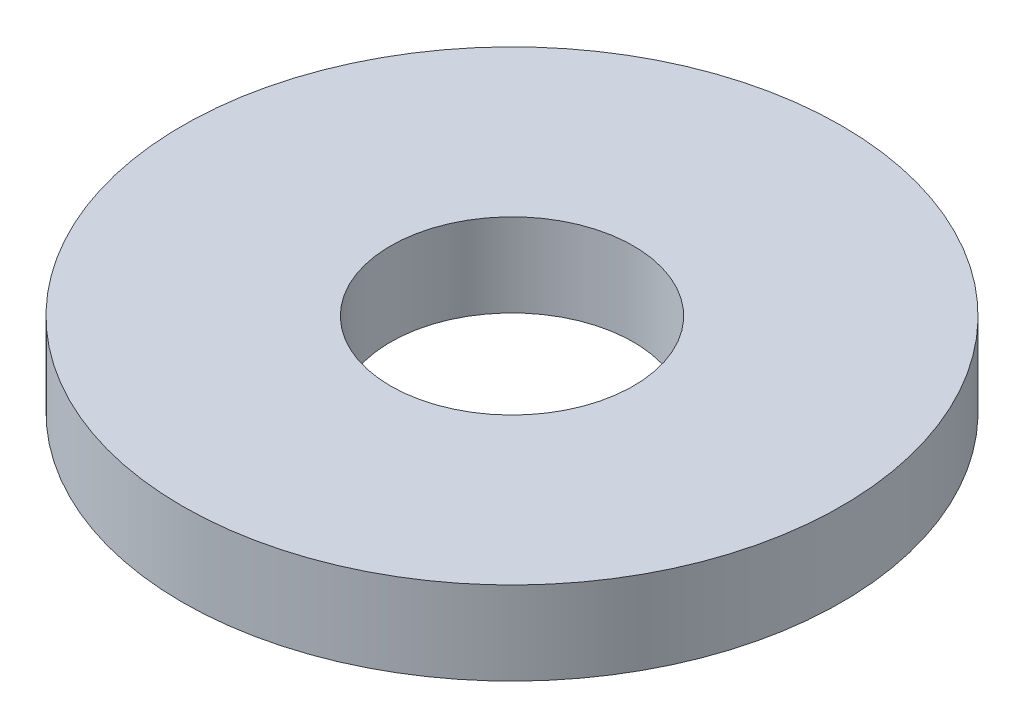
SolidWorks part; units mm, degrees
ref_plane "Front Plane" through (0, 0, 0) normal (0, 0, 1) x (1, 0, 0)
ref_plane "Top Plane" through (0, 0, 0) normal (0, 1, 0) x (1, 0, 0)
ref_plane "Right Plane" through (0, 0, 0) normal (1, 0, 0) x (0, 0, -1)
sketch "Sketch1" plane through (0, 0, 0) normal (0, 1, 0) x (1, 0, 0)
  circle A0 centre (0, 0) radius 95
  dimension "FLANGE_OD" = 190
extrude "Boss-Extrude1" add sketch "Sketch1" along normal blind 24
sketch "Sketch2" plane through (0, 0, 0) normal (0, 1, 0) x (1, 0, 0)
  circle A0 centre (0, 0) radius 35
  dimension "BORE_D" = 70
extrude "Cut-Extrude1" cut sketch "Sketch2" along normal through all
sketch "Sketch3" plane through (0, 24, 0) normal (0, 1, 0) x (1, 0, 0)
  circle A0 centre (0, 0) radius 24.5591 construction
  circle A1 centre (-24.5591, 0) radius 6.5923
  dimension "BOLT_D" = 13.1846
  dimension "BOLT_PCD" = 49.1182
extrude "Cut-Extrude2" cut sketch "Sketch3" against normal blind 20.2955 rebuild error yes
pattern_circular "CirPattern1" count 6 over 360 rebuild error yes
